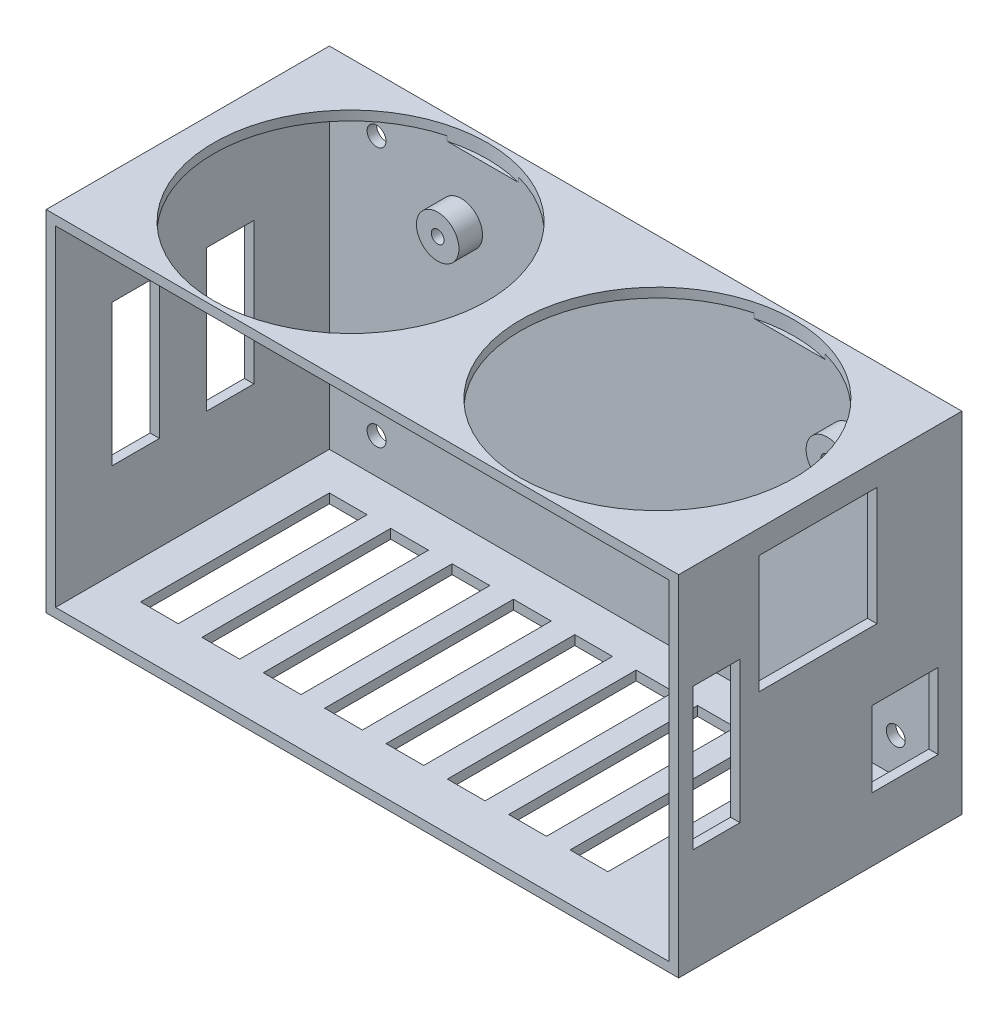
SolidWorks part; units mm, degrees
ref_plane "Plano frontal" through (0, 0, 0) normal (0, 0, 1) x (1, 0, 0)
ref_plane "Plano superior" through (0, 0, 0) normal (0, 1, 0) x (1, 0, 0)
ref_plane "Plano direito" through (0, 0, 0) normal (1, 0, 0) x (0, 0, -1)
sketch "Esboço1" plane through (0, 0, 0) normal (0, 0, 1) x (1, 0, 0)
  line L0 (-67, 37) -> (67, 37)
  line L1 (-65, 35) -> (65, 35)
  line L2 (-65, 35) -> (-65, -35)
  line L3 (-65, -35) -> (65, -35)
  line L4 (65, 35) -> (65, -35)
  line L5 (-65, 35) -> (65, -35) construction
  line L6 (-65, -35) -> (65, 35) construction
  line L7 (67, 37) -> (67, -37)
  line L8 (-67, -37) -> (67, -37)
  line L9 (-67, 37) -> (-67, -37)
  point P0 (0, 0)
  dimension "D2" = 130
  dimension "D3" = 70
  dimension "D1" = 2
extrude "Ressalto-extrusão1" add sketch "Esboço1" along normal blind 60
sketch "Esboço2" plane through (0, 0, 0) normal (0, 0, -1) x (-1, 0, 0)
  line L0 (-67, -37) -> (-67, 37) construction
  line L1 (67, -37) -> (-67, -37) construction
  line L2 (-67, 37) -> (67, 37) construction
  line L3 (67, 37) -> (67, -37) construction
  line L4 (-67, -37) -> (-67, 37)
  line L5 (67, -37) -> (-67, -37)
  line L6 (-67, 37) -> (67, 37)
  line L7 (67, 37) -> (67, -37)
  line L8 (55, 27.5) -> (-55, 27.5) construction
  line L9 (-55, 27.5) -> (-55, -27.5) construction
  line L10 (-55, -27.5) -> (55, -27.5) construction
  line L11 (55, -27.5) -> (55, 27.5) construction
  circle A0 centre (-55, -27.5) radius 2
  circle A1 centre (55, -27.5) radius 2
  circle A2 centre (55, 27.5) radius 2
  circle A3 centre (-55, 27.5) radius 2
  point P12 (0, 27.5)
  point P13 (0, 37)
  point P14 (-55, 0)
  point P15 (-67, 0)
  dimension "D1" = 4
  dimension "D2" = 110
  dimension "D3" = 55
extrude "Ressalto-extrusão2" add sketch "Esboço2" against normal blind 2
sketch "Esboço3" plane through (67, 0, 0) normal (1, 0, 0) x (0, 0, -1)
  line L0 (-60, -37) -> (0, -37) construction
  line L1 (-43, 32) -> (-18, 32)
  line L2 (-43, 32) -> (-43, 7)
  line L3 (-43, 7) -> (-18, 7)
  line L4 (-18, 32) -> (-18, 7)
  line L5 (-19, -7.5) -> (-5, -7.5)
  line L6 (-19, -7.5) -> (-19, -23.5)
  line L7 (-19, -23.5) -> (-5, -23.5)
  line L8 (-5, -7.5) -> (-5, -23.5)
  line L10 (-60, 37) -> (0, 37) construction
  line L11 (-60, -37) -> (-60, 37) construction
  line L12 (-57, 15) -> (-47, 15)
  line L13 (-57, 15) -> (-57, -15)
  line L14 (-57, -15) -> (-47, -15)
  line L15 (-47, 15) -> (-47, -15)
  line L16 (-57, 15) -> (-47, -15) construction
  line L17 (-57, -15) -> (-47, 15) construction
  line L18 (0, -37) -> (0, 37) construction
  point P14 (-52, 0)
  point P23 (-60, 0)
  dimension "D1" = 16
  dimension "D2" = 14
  dimension "D3" = 13.5
  dimension "D4" = 5
  dimension "D5" = 25
  dimension "D6" = 25
  dimension "D7" = 5
  dimension "D8" = 18
  dimension "D9" = 8
  dimension "D10" = 30
  dimension "D11" = 10
extrude "Corte-extrusão1" cut sketch "Esboço3" against normal blind 10
sketch "Esboço6" plane through (0, -37, 0) normal (0, -1, 0) x (1, 0, 0)
  line L1 (-57, 50) -> (-49, 50)
  line L2 (-57, 50) -> (-57, 10)
  line L3 (-57, 10) -> (-49, 10)
  line L4 (-49, 50) -> (-49, 10)
  line L5 (-67, 60) -> (-67, 0) construction
  line L6 (-44, 50) -> (-36, 50)
  line L7 (-44, 50) -> (-44, 10)
  line L8 (-44, 10) -> (-36, 10)
  line L9 (-36, 50) -> (-36, 10)
  line L10 (-31, 50) -> (-23, 50)
  line L11 (-31, 50) -> (-31, 10)
  line L12 (-31, 10) -> (-23, 10)
  line L13 (-23, 50) -> (-23, 10)
  line L14 (-18, 50) -> (-10, 50)
  line L15 (-18, 50) -> (-18, 10)
  line L16 (-18, 10) -> (-10, 10)
  line L17 (-10, 50) -> (-10, 10)
  line L18 (-5, 50) -> (3, 50)
  line L19 (-5, 50) -> (-5, 10)
  line L20 (-5, 10) -> (3, 10)
  line L21 (3, 50) -> (3, 10)
  line L22 (8, 50) -> (16, 50)
  line L23 (8, 50) -> (8, 10)
  line L24 (8, 10) -> (16, 10)
  line L25 (16, 50) -> (16, 10)
  line L26 (21, 50) -> (29, 50)
  line L27 (21, 50) -> (21, 10)
  line L28 (21, 10) -> (29, 10)
  line L29 (29, 50) -> (29, 10)
  line L30 (34, 50) -> (42, 50)
  line L31 (34, 50) -> (34, 10)
  line L32 (34, 10) -> (42, 10)
  line L33 (42, 50) -> (42, 10)
  line L34 (67, 60) -> (67, 0) construction
  point P4 (-57, 30)
  point P37 (67, 30)
  dimension "D1" = 8
  dimension "D2" = 40
  dimension "D4" = 10
  dimension "D5" = 8
extrude "Corte-extrusão2" cut sketch "Esboço6" against normal blind 10
sketch "Esboço7" plane through (-67, 0, 0) normal (-1, 0, 0) x (0, 0, 1)
  line L1 (48, 15) -> (38, 15)
  line L2 (48, 15) -> (48, -15)
  line L3 (48, -15) -> (38, -15)
  line L4 (38, 15) -> (38, -15)
  line L5 (48, 15) -> (38, -15) construction
  line L6 (48, -15) -> (38, 15) construction
  line L7 (28, 15) -> (18, 15)
  line L8 (28, 15) -> (28, -15)
  line L9 (28, -15) -> (18, -15)
  line L10 (18, 15) -> (18, -15)
  line L11 (28, 15) -> (18, -15) construction
  line L12 (28, -15) -> (18, 15) construction
  line L13 (0, 37) -> (0, -37) construction
  point P0 (43, 0)
  point P5 (23, 0)
  dimension "D1" = 10
  dimension "D2" = 30
  dimension "D3" = 10
  dimension "D4" = 18
extrude "Corte-extrusão3" cut sketch "Esboço7" against normal blind 12
sketch "Esboço8" plane through (0, 0, 2) normal (0, 0, -1) x (-1, 0, 0)
  line L0 (-65, -35) -> (-65, 35) construction
  line L1 (-65, 35) -> (65, 35) construction
  circle A0 centre (-44.2, -26.5) radius 4.5
  circle A1 centre (-44.2, -26.5) radius 1.35
  circle A2 centre (37.05, 20.5) radius 4.5
  circle A3 centre (37.05, 20.5) radius 1.35
  circle A4 centre (-45.5, 20.5) radius 1.35
  circle A5 centre (-45.5, 20.5) radius 1.35
  circle A6 centre (-45.5, 20.5) radius 4.5
  point P5 (0, 0)
  point P11 (-38.65, 20.6)
  point P13 (0, 0)
  point P17 (76.1764, 14.7094)
  point P18 (0, 0)
  dimension "D1" = 9
  dimension "D2" = 2.7
  dimension "D3" = 82.55
  dimension "D4" = 47
  dimension "D5" = 1.3
  dimension "D6" = 19.5
  dimension "D7" = 14.5
extrude "Ressalto-extrusão3" add sketch "Esboço8" against normal blind 5 contours A2 A3 | A6 A4 | A0 A1 region at (48.5727, -26.5, 2) region at (-32.6773, 20.5, 2) region at (49.8727, 20.5, 2)
extrude "Corte-extrusão4" cut sketch "Esboço8<3>" along normal through all contours A4 | A3 | A1
sketch "Esboço8<3>" plane through (0, 0, 2) normal (0, 0, -1) x (-1, 0, 0) same geometry as "Esboço8"
sketch "Esboço9" plane through (0, 0, 2) normal (0, 0, 1) x (1, 0, 0)
  circle A0 centre (45.5, 20.5) radius 3
  circle A1 centre (44.2, -26.5) radius 3
  circle A2 centre (-37.05, 20.5) radius 3
  circle A3 centre (44.2, -26.5) radius 1.35 construction
  point P8 (-38.7, 20.5)
  point P9 (0, 0)
  point P10 (41.5, 20.5)
  point P11 (49.5762, -17.7142)
  dimension "D1" = 6
extrude "Corte-extrusão5" cut sketch "Esboço9" along normal offset from surface (2 mm away) 3 up to face at (-32.55, 20.5, 7)
sketch "Esboço10" plane through (0, 37, 0) normal (0, 1, 0) x (1, 0, 0)
  line L0 (32.5, -30) -> (-32.5, -30) construction
  line L1 (67, -60) -> (-67, -60) construction
  line L2 (67, -60) -> (67, 0) construction
  circle A0 centre (32.5, -30) radius 29
  circle A1 centre (-32.5, -30) radius 29
  point P4 (0, -30)
  point P7 (0, -60)
  point P10 (67, -30)
  dimension "D2" = 58
  dimension "D1" = 65
extrude "Corte-extrusão6" cut sketch "Esboço10" against normal blind 3
